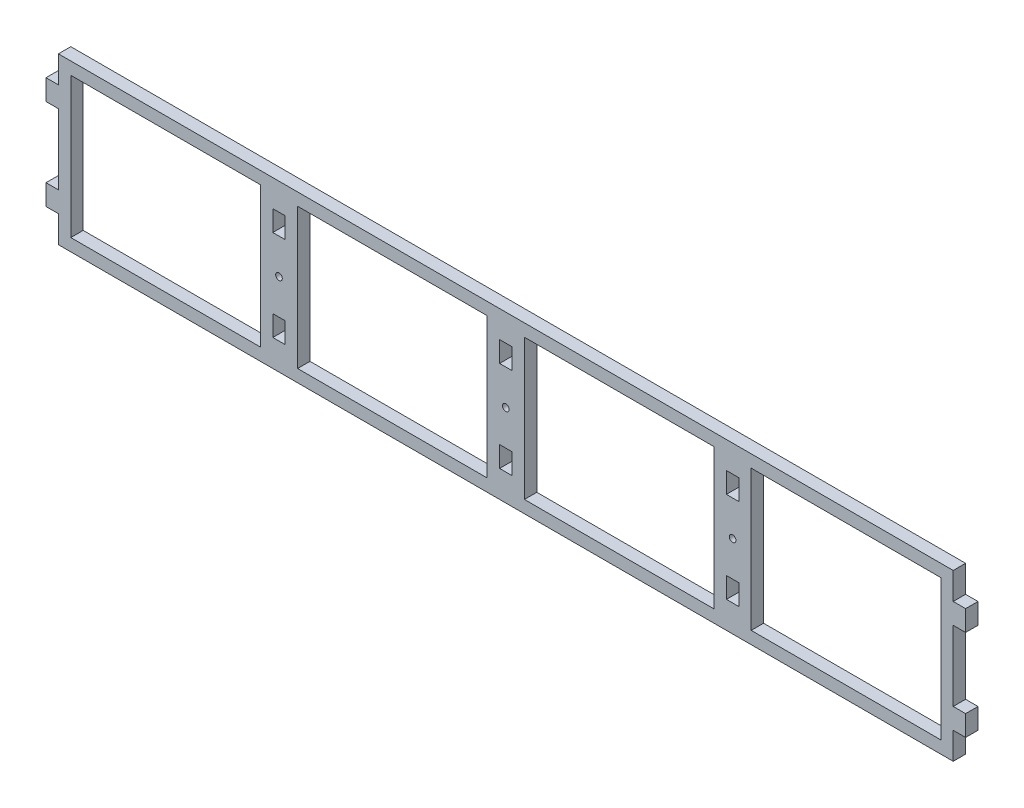
SolidWorks part; units mm, degrees
ref_plane "Front Plane" through (0, 0, 0) normal (0, 0, 1) x (1, 0, 0)
ref_plane "Top Plane" through (0, 0, 0) normal (0, 1, 0) x (1, 0, 0)
ref_plane "Right Plane" through (0, 0, 0) normal (1, 0, 0) x (0, 0, -1)
sketch "Sketch1" plane through (0, 0, 0) normal (0, 0, 1) x (1, 0, 0)
  line L1 (-216.5, -40) -> (216.5, -40)
  line L2 (-216.5, -40) -> (-216.5, 40)
  line L3 (-216.5, 40) -> (216.5, 40)
  line L4 (216.5, -40) -> (216.5, 40)
  line L5 (-216.5, -40) -> (216.5, 40) construction
  line L6 (-216.5, 40) -> (216.5, -40) construction
  point P0 (0, 0)
  dimension "D1" = 433
  dimension "D2" = 80
extrude "Boss-Extrude1" add sketch "Sketch1" along normal blind 6
sketch "Sketch2" plane through (0, 0, 6) normal (0, 0, 1) x (1, 0, 0)
  line L0 (-118.75, -40) -> (-118.75, -27) construction
  line L8 (216.5, -40) -> (216.5, 40)
  line L9 (216.5, 40) -> (-216.5, 40)
  line L10 (-216.5, 40) -> (-216.5, -40)
  line L11 (-216.5, -40) -> (216.5, -40)
  line L12 (216.5, -40) -> (216.5, 40)
  line L13 (216.5, 40) -> (-216.5, 40)
  line L14 (-216.5, 40) -> (-216.5, -40)
  line L15 (-216.5, -40) -> (216.5, -40)
  line L16 (-112.75, -40) -> (-112.75, -27) construction
  line L17 (-112.75, -40) -> (-112.75, -27) construction
  line L18 (-118.75, -34) -> (-118.75, 34)
  line L19 (-216.5, -34) -> (216.5, -34)
  line L20 (-210.5, 40) -> (-210.5, -40)
  line L21 (-118.75, 34) -> (-210.5, 34)
  dimension "D5" = 6
  dimension "D1" = 0
  dimension "D2" = 6
  dimension "D3" = 6
  dimension "D4" = 6
extrude "Cut-Extrude1" cut sketch "Sketch2" against normal up to next contours L18 L21 L20 L19 region at (-164.625, 0, 6)
pattern_linear "LPattern1" count 4 spacing 109.75 along (1, 0, 0) of "Cut-Extrude1"
sketch "Sketch3" plane through (0, 0, 0) normal (0, 0, -1) x (-1, 0, 0)
  line L8 (-112.75, -27) -> (-112.75, -17) construction
  line L9 (-112.75, -17) -> (-106.75, -17) construction
  line L10 (-106.75, -17) -> (-106.75, -27) construction
  line L11 (-106.75, -27) -> (-112.75, -27) construction
  line L12 (-112.75, 17) -> (-112.75, 27) construction
  line L13 (-112.75, 27) -> (-106.75, 27) construction
  line L14 (-106.75, 27) -> (-106.75, 17) construction
  line L15 (-106.75, 17) -> (-112.75, 17) construction
  line L24 (-112.75, -27) -> (-112.75, -17)
  line L25 (-112.75, -17) -> (-106.75, -17)
  line L26 (-106.75, -17) -> (-106.75, -27)
  line L27 (-106.75, -27) -> (-112.75, -27)
  line L28 (-112.75, 17) -> (-112.75, 27)
  line L29 (-112.75, 27) -> (-106.75, 27)
  line L30 (-106.75, 27) -> (-106.75, 17)
  line L31 (-106.75, 17) -> (-112.75, 17)
  line L40 (-3, 17) -> (-3, 27) construction
  line L41 (-3, 27) -> (3, 27) construction
  line L42 (3, 27) -> (3, 17) construction
  line L43 (3, 17) -> (-3, 17) construction
  line L44 (-3, -27) -> (-3, -17) construction
  line L45 (-3, -17) -> (3, -17) construction
  line L46 (3, -17) -> (3, -27) construction
  line L47 (3, -27) -> (-3, -27) construction
  line L48 (-3, 17) -> (-3, 27)
  line L49 (-3, 27) -> (3, 27)
  line L50 (3, 27) -> (3, 17)
  line L51 (3, 17) -> (-3, 17)
  line L52 (-3, -27) -> (-3, -17)
  line L53 (-3, -17) -> (3, -17)
  line L54 (3, -17) -> (3, -27)
  line L55 (3, -27) -> (-3, -27)
  line L56 (106.75, 17) -> (106.75, 27) construction
  line L57 (106.75, 27) -> (112.75, 27) construction
  line L58 (112.75, 27) -> (112.75, 17) construction
  line L59 (112.75, 17) -> (106.75, 17) construction
  line L60 (106.75, -27) -> (106.75, -17) construction
  line L61 (106.75, -17) -> (112.75, -17) construction
  line L62 (112.75, -17) -> (112.75, -27) construction
  line L63 (112.75, -27) -> (106.75, -27) construction
  line L64 (106.75, 17) -> (106.75, 27)
  line L65 (106.75, 27) -> (112.75, 27)
  line L66 (112.75, 27) -> (112.75, 17)
  line L67 (112.75, 17) -> (106.75, 17)
  line L68 (106.75, -27) -> (106.75, -17)
  line L69 (106.75, -17) -> (112.75, -17)
  line L70 (112.75, -17) -> (112.75, -27)
  line L71 (112.75, -27) -> (106.75, -27)
  circle A3 centre (109.75, 0) radius 1.6 construction
  circle A4 centre (0, 0) radius 1.6 construction
  circle A5 centre (-109.75, 0) radius 1.6 construction
  circle A6 centre (109.75, 0) radius 1.6
  circle A7 centre (0, 0) radius 1.6
  circle A8 centre (-109.75, 0) radius 1.6
extrude "Cut-Extrude2" cut sketch "Sketch3" against normal through all
sketch "Sketch4" plane through (0, 0, 0) normal (0, 0, -1) x (-1, 0, 0)
  line L0 (-112.75, 17) -> (-216.5, 17) construction
  line L1 (-216.5, -40) -> (-216.5, 40) construction
  line L2 (-109.75, 0) -> (-216.5, 0) construction
  line L3 (-222.5, 21.3321) -> (-222.5, 40) construction
  line L4 (-216.5, 17) -> (-222.5, 17)
  line L5 (-216.5, 17) -> (-216.5, 27)
  line L6 (-216.5, 27) -> (-222.5, 27)
  line L7 (-222.5, 17) -> (-222.5, 27)
  line L8 (-112.75, 27) -> (-112.75, 17) construction
  line L9 (-222.5, -17) -> (-222.5, -27)
  line L10 (-216.5, -27) -> (-222.5, -27)
  line L11 (-216.5, -17) -> (-216.5, -27)
  line L12 (-216.5, -17) -> (-222.5, -17)
  line L13 (0, 0) -> (0, 40) construction
  line L14 (-216.5, 40) -> (216.5, 40) construction
  line L15 (216.5, -17) -> (222.5, -17)
  line L16 (216.5, -17) -> (216.5, -27)
  line L17 (216.5, -27) -> (222.5, -27)
  line L18 (222.5, -17) -> (222.5, -27)
  line L19 (222.5, 17) -> (222.5, 27)
  line L20 (216.5, 27) -> (222.5, 27)
  line L21 (216.5, 17) -> (216.5, 27)
  line L22 (216.5, 17) -> (222.5, 17)
extrude "Boss-Extrude2" add sketch "Sketch4" against normal blind 6
